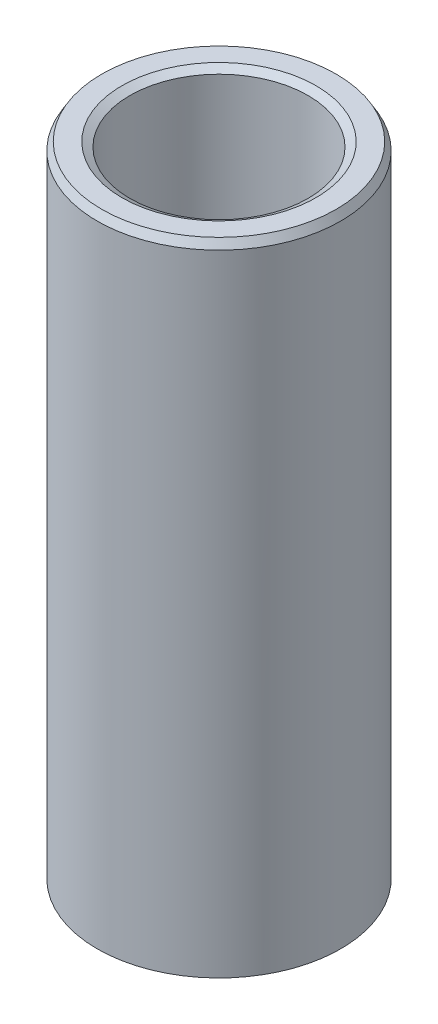
SolidWorks part; units mm, degrees
ref_plane "Front Plane" through (0, 0, 0) normal (0, 0, 1) x (1, 0, 0)
ref_plane "Top Plane" through (0, 0, 0) normal (0, 1, 0) x (1, 0, 0)
ref_plane "Right Plane" through (0, 0, 0) normal (1, 0, 0) x (0, 0, -1)
sketch "Sketch1" plane through (0, 0, 0) normal (0, 1, 0) x (1, 0, 0)
  circle A0 centre (0, 0) radius 52.5
  dimension "SLEEVE_OD" = 105
extrude "Boss-Extrude1" add sketch "Sketch1" along normal blind 277.1432
sketch "Sketch2" plane through (0, 0, 0) normal (0, 1, 0) x (1, 0, 0)
  circle A0 centre (0, 0) radius 38.4396
  dimension "BORE_D" = 76.8792
extrude "Cut-Extrude1" cut sketch "Sketch2" along normal through all
chamfer "Chamfer1" distance 3.4061 angle 30 4 edges at (0, 277.1432, 38.4396) (0, 0, 38.4396) (0, 0, 52.5) (0, 277.1432, 52.5) first distance on face at (0, 277.1432, 38.4396) first distance on face at (0, 0, 38.4396) first distance on face at (0, 277.1432, 52.5)
